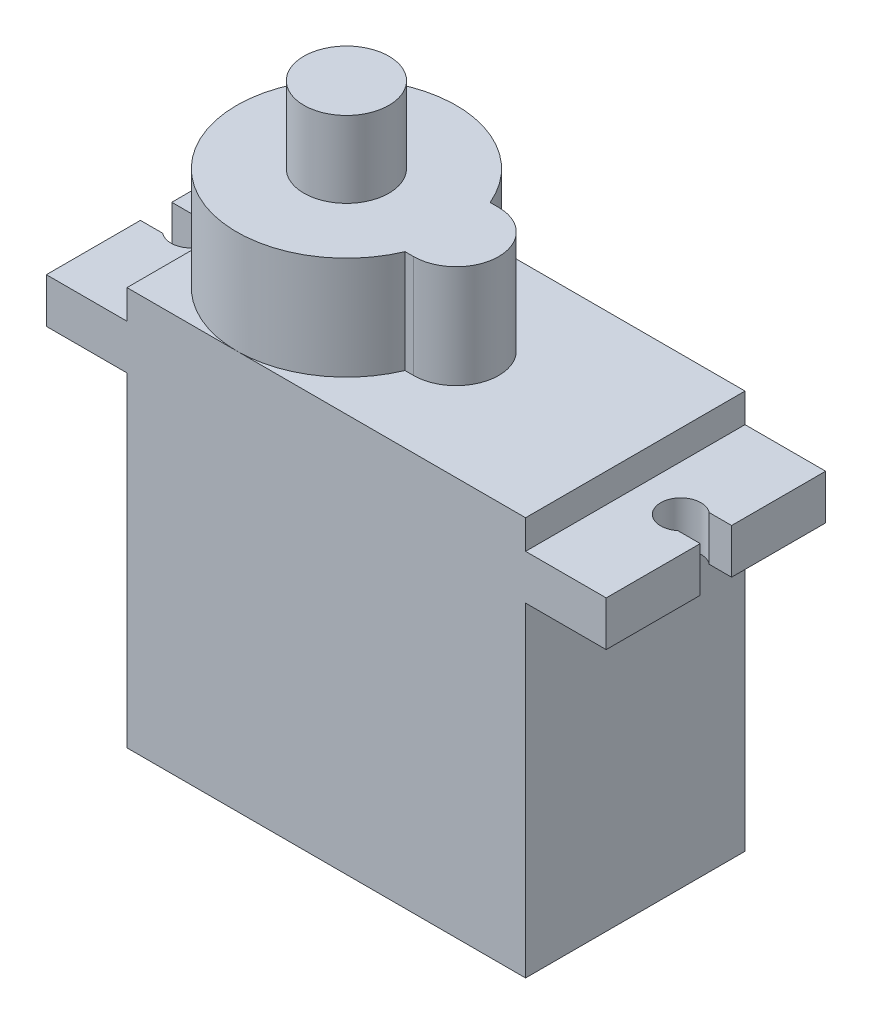
SolidWorks part; units mm, degrees
ref_plane "Front Plane" through (0, 0, 0) normal (0, 0, 1) x (1, 0, 0)
ref_plane "Top Plane" through (0, 0, 0) normal (0, 1, 0) x (1, 0, 0)
ref_plane "Right Plane" through (0, 0, 0) normal (1, 0, 0) x (0, 0, -1)
sketch "Sketch1" plane through (0, 0, 0) normal (0, 1, 0) x (1, 0, 0)
  line L1 (11.303, -6.223) -> (-11.303, -6.223)
  line L2 (11.303, -6.223) -> (11.303, 6.223)
  line L3 (11.303, 6.223) -> (-11.303, 6.223)
  line L4 (-11.303, -6.223) -> (-11.303, 6.223)
  line L5 (11.303, -6.223) -> (-11.303, 6.223) construction
  line L6 (11.303, 6.223) -> (-11.303, -6.223) construction
  point P0 (0, 0)
  dimension "D1" = 22.606
  dimension "D2" = 12.446
extrude "Boss-Extrude1" add sketch "Sketch1" along normal blind 18.415
sketch "Sketch2" plane through (0, 18.415, 0) normal (0, 1, 0) x (1, 0, 0)
  line L0 (0, 6.223) -> (-17.0969, 6.223) construction
  line L1 (11.303, 6.223) -> (-11.303, 6.223) construction
  line L2 (-11.303, 6.223) -> (-11.303, -6.223) construction
  line L3 (15.875, -6.223) -> (-15.875, -6.223)
  line L4 (15.875, -6.223) -> (15.875, 6.223) construction
  line L5 (15.875, 6.223) -> (-15.875, 6.223)
  line L6 (-15.875, -6.223) -> (-15.875, 6.223) construction
  line L7 (15.875, -6.223) -> (-15.875, 6.223) construction
  line L8 (15.875, 6.223) -> (-15.875, -6.223) construction
  line L9 (-15.875, 6.223) -> (-15.875, 0.889)
  line L10 (-15.875, 0.889) -> (-14.605, 0.889)
  line L11 (-15.875, 0) -> (-12.9515, 0) construction
  line L12 (-15.875, -0.889) -> (-14.605, -0.889)
  line L13 (-15.875, -6.223) -> (-15.875, -0.889)
  line L14 (0, 0) -> (0, 6.223) construction
  line L15 (15.875, -6.223) -> (15.875, -0.889)
  line L16 (15.875, -0.889) -> (14.605, -0.889)
  line L17 (15.875, 0.889) -> (14.605, 0.889)
  line L18 (15.875, 6.223) -> (15.875, 0.889)
  circle A0 centre (-13.8866, 0) radius 1.143 construction
  arc A1 (-14.605, 0.889) -> (-14.605, -0.889) centre (-13.8866, 0) cw
  arc A2 (14.605, 0.889) -> (14.605, -0.889) centre (13.8866, 0) ccw
  point P4 (0, 0)
  dimension "D4" = 2.286
  dimension "D1" = 4.572
  dimension "D2" = 5.334
  dimension "D3" = 1.27
extrude "Boss-Extrude2" add sketch "Sketch2" along normal blind 2.54
sketch "Sketch3" plane through (0, 20.955, 0) normal (0, 1, 0) x (1, 0, 0)
  line L0 (15.875, 6.223) -> (-15.875, 6.223) construction
  line L1 (11.303, -6.223) -> (-11.303, -6.223)
  line L2 (11.303, -6.223) -> (11.303, 6.223)
  line L3 (11.303, 6.223) -> (-11.303, 6.223)
  line L4 (-11.303, -6.223) -> (-11.303, 6.223)
  line L5 (11.303, -6.223) -> (-11.303, 6.223) construction
  line L6 (11.303, 6.223) -> (-11.303, -6.223) construction
  point P0 (0, 0)
  dimension "D1" = 22.606
extrude "Boss-Extrude3" add sketch "Sketch3" along normal blind 1.651
sketch "Sketch4" plane through (0, 22.606, 0) normal (0, 1, 0) x (1, 0, 0)
  line L0 (-5.08, -6.223) -> (-5.08, 0) construction
  line L1 (-11.303, -6.223) -> (11.303, -6.223) construction
  line L2 (-5.08, 0) -> (-11.303, 0) construction
  line L3 (-11.303, 6.223) -> (-11.303, -6.223) construction
  line L4 (1.143, 2.413) -> (0.6561, 2.413)
  line L5 (1.143, -2.413) -> (0.6561, -2.413)
  circle A0 centre (-5.08, 0) radius 6.223 construction
  circle A1 centre (1.143, 0) radius 2.413 construction
  arc A2 (0.6561, 2.413) -> (-11.303, 0) centre (-5.08, 0) ccw
  arc A3 (1.143, -2.413) -> (1.143, 2.413) centre (1.143, 0) ccw
  arc A4 (0.6561, -2.413) -> (-11.303, 0) centre (-5.08, 0) cw
  dimension "D1" = 4.826
  dimension "D2" = 12.446
  dimension "D4" = 0.4869
extrude "Boss-Extrude4" add sketch "Sketch4" along normal blind 5.842 contours A4 L5 A3 L4 A2 region at (-4.5407, 22.606, 0)
sketch "Sketch5" plane through (0, 28.448, 0) normal (0, 1, 0) x (1, 0, 0)
  line L0 (-5.08, 6.223) -> (-5.08, 0) construction
  line L1 (-11.303, 0) -> (-5.08, 0) construction
  arc A0 (0.6561, 2.413) -> (0.6561, -2.413) centre (-5.08, 0) ccw construction
  circle A1 centre (-5.08, 0) radius 2.413
  dimension "D1" = 4.826
extrude "Boss-Extrude5" add sketch "Sketch5" along normal blind 4.318
